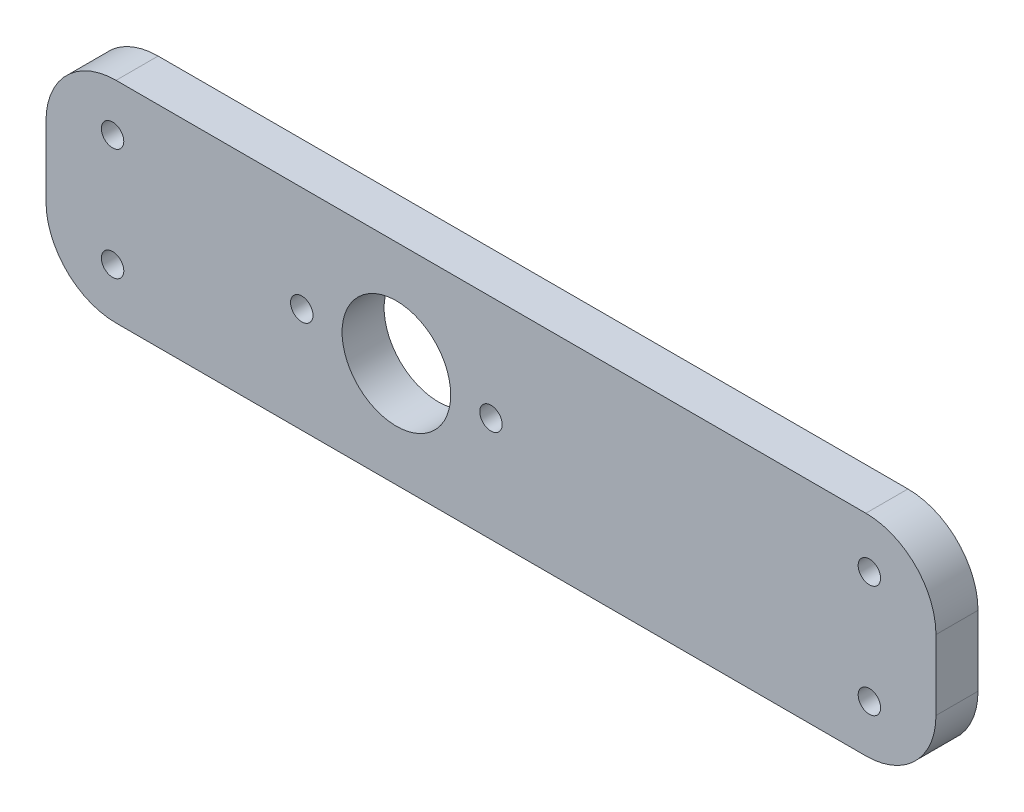
SolidWorks part; units mm, degrees
material "MDF"
ref_plane "Plano frontal" through (0, 0, 0) normal (0, 0, 1) x (1, 0, 0)
ref_plane "Plano superior" through (0, 0, 0) normal (0, 1, 0) x (1, 0, 0)
ref_plane "Plano direito" through (0, 0, 0) normal (1, 0, 0) x (0, 0, -1)
sketch "Esboço1" plane through (0, 0, 0) normal (0, 0, 1) x (1, 0, 0)
  line L0 (-27, 0) -> (0, 0) construction
  line L1 (-63.5, -15) -> (63.5, -15)
  line L2 (-63.5, -15) -> (-63.5, 15)
  line L3 (-63.5, 15) -> (63.5, 15)
  line L4 (63.5, -15) -> (63.5, 15)
  line L5 (0, 15) -> (0, -15) construction
  line L6 (-63.5, 0) -> (63.5, 0) construction
  line L7 (44.5, 15) -> (44.5, -15) construction
  line L8 (-44.5, 15) -> (-44.5, -15) construction
  line L9 (-44.5, 5.3275) -> (-63.5, 5.3275) construction
  circle A0 centre (-13.5, 0) radius 7.75
  circle A1 centre (0, 0) radius 1.6
  circle A2 centre (-27, 0) radius 1.6
  circle A4 centre (-54, 8) radius 1.6
  circle A5 centre (-54, -8) radius 1.6
  circle A6 centre (54, -8) radius 1.6
  circle A7 centre (54, 8) radius 1.6
  point P0 (0, 0)
  point P21 (-54, 5.3275)
  dimension "D1" = 3.2
  dimension "D2" = 15.5
  dimension "D4" = 31
  dimension "D9" = 16
  dimension "D3" = 27
  dimension "D5" = 15
  dimension "D6" = 19
  dimension "D7" = 58
  dimension "D8" = 30
extrude "Ressalto-extrusão1" add sketch "Esboço1" along normal blind 6
fillet "Filete1" radius 10 4 edges at (-63.5, 15, 3) (-63.5, -15, 3) (63.5, -15, 3) (63.5, 15, 3)
